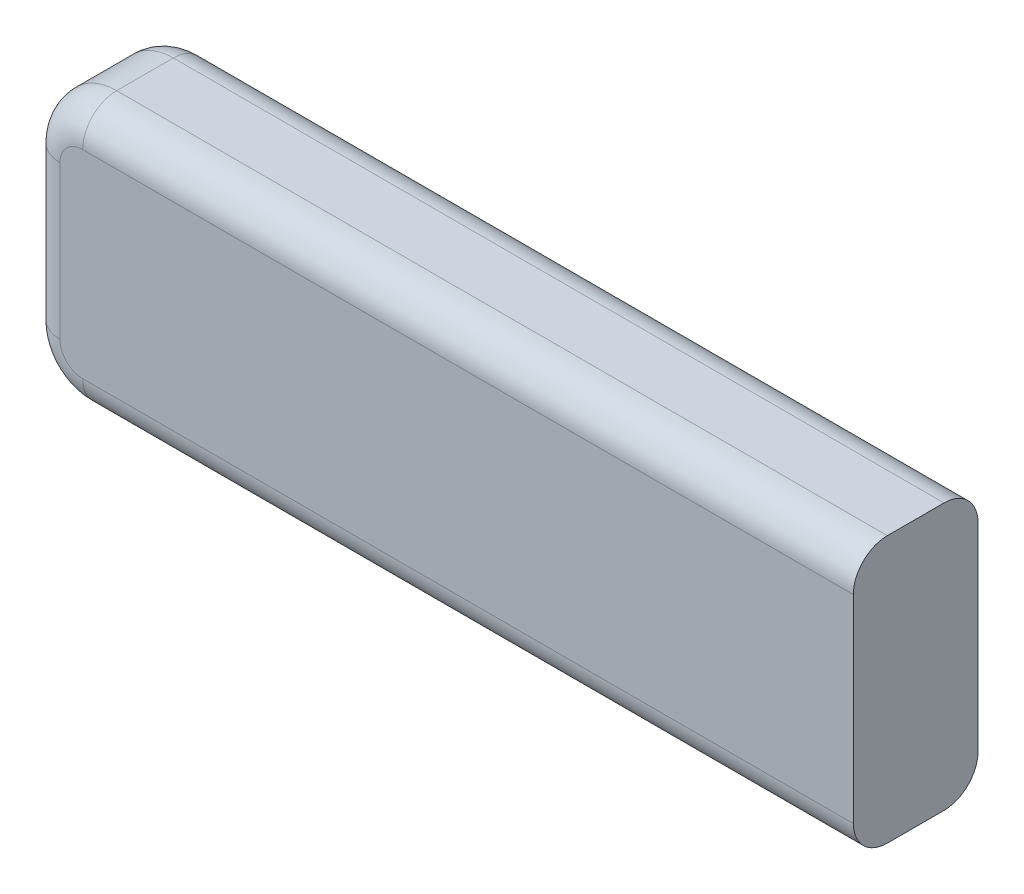
SolidWorks part; units mm, degrees
ref_plane "Front" through (0, 0, 0) normal (0, 0, 1) x (1, 0, 0)
ref_plane "Top" through (0, 0, 0) normal (0, 1, 0) x (1, 0, 0)
ref_plane "Right" through (0, 0, 0) normal (1, 0, 0) x (0, 0, -1)
sketch "Sketch1" plane through (0, 0, 0) normal (0, 0, 1) x (1, 0, 0)
  line L1 (0, 0) -> (36.5, 0)
  line L2 (0, 0) -> (0, 11.75)
  line L3 (0, 11.75) -> (36.5, 11.75)
  line L4 (36.5, 0) -> (36.5, 11.75)
  dimension "D1" = 11.75
  dimension "D2" = 36.5
extrude "Boss-Extrude1" add sketch "Sketch1" along normal blind 5.5
fillet "Body Fillet" radius 1.5 6 edges at (18.25, 0, 0) (18.25, 0, 5.5) (0, 5.875, 0) (0, 5.875, 5.5) (18.25, 11.75, 0) (18.25, 11.75, 5.5)
fillet "Fillet1" radius 2.5 6 edges at (0.4393, 0.4393, 0.4393) (0.4393, 0.4393, 5.0607) (0.4393, 11.3107, 0.4393) (0.4393, 11.3107, 5.0607) (0, 11.75, 2.75) (0, 0, 2.75)
